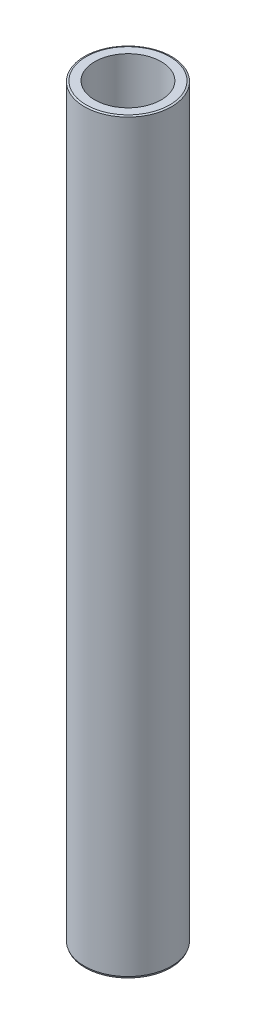
SolidWorks part; units mm, degrees
ref_plane "Front Plane" through (0, 0, 0) normal (0, 0, 1) x (1, 0, 0)
ref_plane "Top Plane" through (0, 0, 0) normal (0, 1, 0) x (1, 0, 0)
ref_plane "Right Plane" through (0, 0, 0) normal (1, 0, 0) x (0, 0, -1)
sketch "Sketch1" plane through (0, 0, 0) normal (0, 1, 0) x (1, 0, 0)
  circle A0 centre (0, 0) radius 35
  dimension "SHAFT_OD" = 70
extrude "Boss-Extrude1" add sketch "Sketch1" along normal blind 600
sketch "Sketch2" plane through (0, 0, 0) normal (0, 1, 0) x (1, 0, 0)
  circle A0 centre (0, 0) radius 26.6832
  dimension "BORE_D" = 53.3664
extrude "Cut-Extrude1" cut sketch "Sketch2" along normal through all
chamfer "Chamfer1" distance 0.562 angle 68.395 2 edges at (0, 600, 35) (0, 0, 35) first distance on face at (0, 600, 35) first distance on face at (0, 0, 26.6832)
